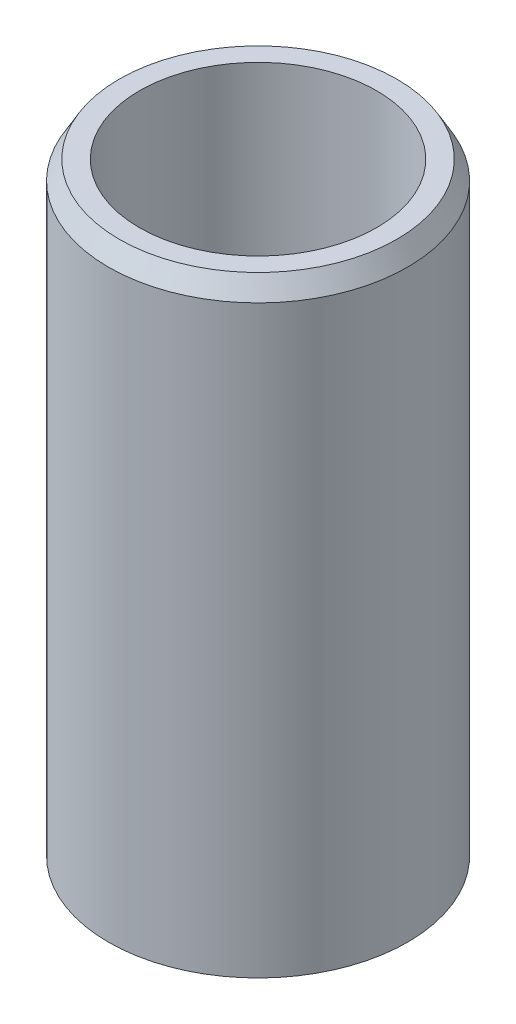
SolidWorks part; units mm, degrees
ref_plane "Front Plane" through (0, 0, 0) normal (0, 0, 1) x (1, 0, 0)
ref_plane "Top Plane" through (0, 0, 0) normal (0, 1, 0) x (1, 0, 0)
ref_plane "Right Plane" through (0, 0, 0) normal (1, 0, 0) x (0, 0, -1)
sketch "Sketch1" plane through (0, 0, 0) normal (0, 1, 0) x (1, 0, 0)
  circle A0 centre (0, 0) radius 42.5
  dimension "SHAFT_OD" = 85
extrude "Boss-Extrude1" add sketch "Sketch1" along normal blind 174.4864
sketch "Sketch2" plane through (0, 0, 0) normal (0, 1, 0) x (1, 0, 0)
  circle A0 centre (0, 0) radius 33.7083
  dimension "BORE_D" = 67.4166
extrude "Cut-Extrude1" cut sketch "Sketch2" along normal through all
chamfer "Chamfer1" distance 5.3158 angle 30 2 edges at (0, 174.4864, 42.5) (0, 0, 42.5) first distance on face at (0, 174.4864, 42.5) first distance on face at (0, 0, 33.7083)
